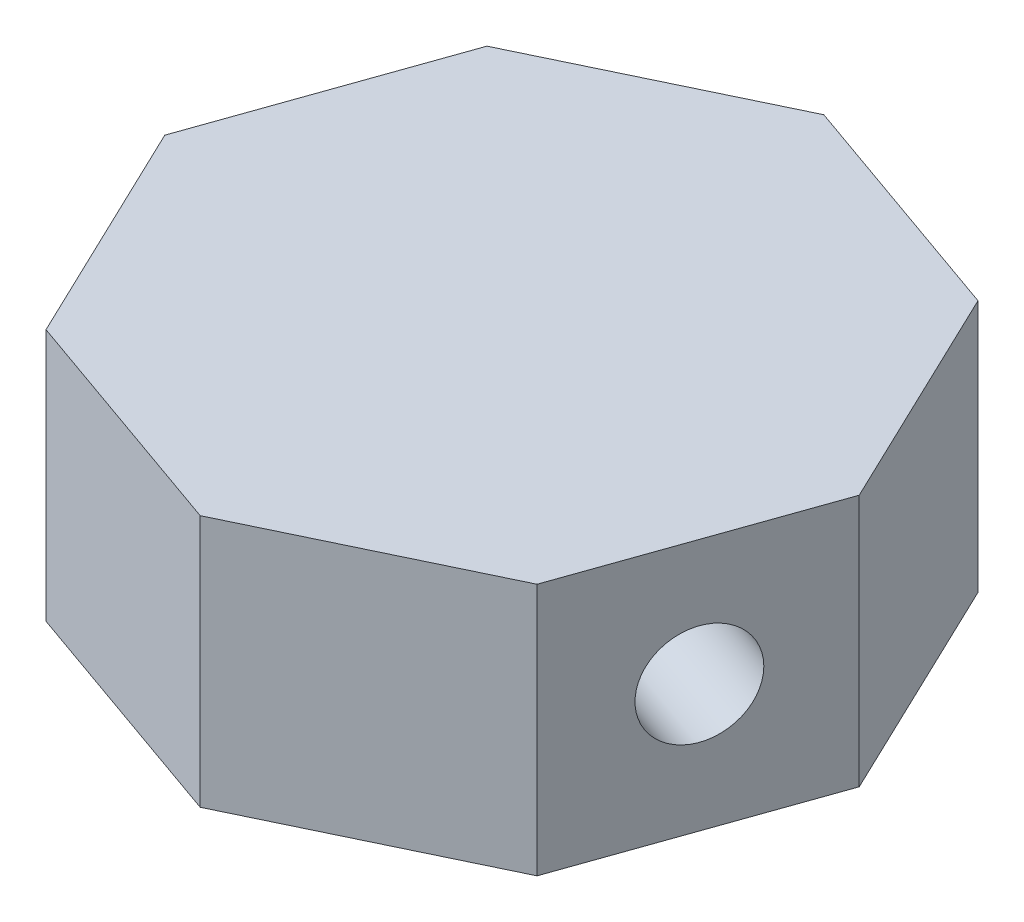
SolidWorks part; units mm, degrees
ref_plane "Front Plane" through (0, 0, 0) normal (0, 0, 1) x (1, 0, 0)
ref_plane "Top Plane" through (0, 0, 0) normal (0, 1, 0) x (1, 0, 0)
ref_plane "Right Plane" through (0, 0, 0) normal (1, 0, 0) x (0, 0, -1)
sketch "Sketch1" plane through (0, 0, 0) normal (0, 1, 0) x (1, 0, 0)
  line L1 (78.512, -146.1841) -> (158.8841, -47.8514)
  line L2 (158.8841, -47.8514) -> (146.1841, 78.512)
  line L3 (146.1841, 78.512) -> (47.8514, 158.8841)
  line L4 (47.8514, 158.8841) -> (-78.512, 146.1841)
  line L5 (-78.512, 146.1841) -> (-158.8841, 47.8514)
  line L6 (-158.8841, 47.8514) -> (-146.1841, -78.512)
  line L7 (-146.1841, -78.512) -> (-47.8514, -158.8841)
  line L9 (-47.8514, -158.8841) -> (78.512, -146.1841) [skipped]
  line L10 (4.8364, 12.0753) -> (-0.6466, 23.5308)
  line L11 (-0.6466, 23.5308) -> (-12.6238, 27.7539)
  line L12 (-12.6238, 27.7539) -> (-24.0793, 22.271)
  line L13 (-24.0793, 22.271) -> (-28.3024, 10.2937)
  line L14 (-28.3024, 10.2937) -> (-22.8195, -1.1617)
  line L15 (-22.8195, -1.1617) -> (-10.8422, -5.3849)
  line L16 (-10.8422, -5.3849) -> (0.6132, 0.0981)
  line L17 (0.6132, 0.0981) -> (4.8364, 12.0753)
  circle A0 centre (0, 0) radius 153.3026 construction
  circle A1 centre (-11.733, 11.1845) radius 15.3303 construction
  dimension "D1" = 12.7
  dimension "D2" = 12.7
extrude "Boss-Extrude1" add sketch "Sketch1" along normal blind 12.7 contours L16 L17 L10 L11 L12 L13 L14 L15 region at (-11.733, 0, -11.1845)
sketch "Sketch2" plane through (0.5147, 0, 0.1815) normal (0.9431, 0, 0.3325) x (0.3325, 0, -0.9431)
  line L0 (12.9964, 12.7) -> (0.2964, 0)
  line L1 (0.2964, 0) -> (12.9964, 0)
  line L2 (12.9964, 0) -> (0.2964, 12.7)
  circle A0 centre (6.6964, 6.4) radius 2.54
extrude "Cut-Extrude1" cut sketch "Sketch2" against normal blind 12.7 contours L2 A0 L0 | L0 A0 L2 | L2 A0 L0 | L0 A0 L2 region at (3.241, 6.3684, -7.5506) region at (2.731, 7.9022, -6.1041) region at (2.7308, 4.8534, -6.1036) region at (2.2271, 6.3679, -4.6752)
sketch "Sketch3" plane through (0, 0, 0) normal (0, -1, 0) x (1, 0, 0)
  line L0 (-0.6466, -23.5308) -> (-22.918, 1.2089)
  line L1 (-22.918, 1.2089) -> (-28.3024, -10.2937)
  line L2 (-28.3024, -10.2937) -> (4.8364, -12.0753)
  circle A0 centre (-11.7823, -11.1609) radius 3.175
extrude "Cut-Extrude2" cut sketch "Sketch3" against normal blind 2.54 contours L2 A0 L0 | L0 A0 L2 | L2 A0 L0 | L0 A0 L2 region at (-12.4929, 0, -12.6671) region at (-9.9164, 0, -12.0639) region at (-13.6389, 0, -10.285) region at (-11.0619, 0, -9.6725)
